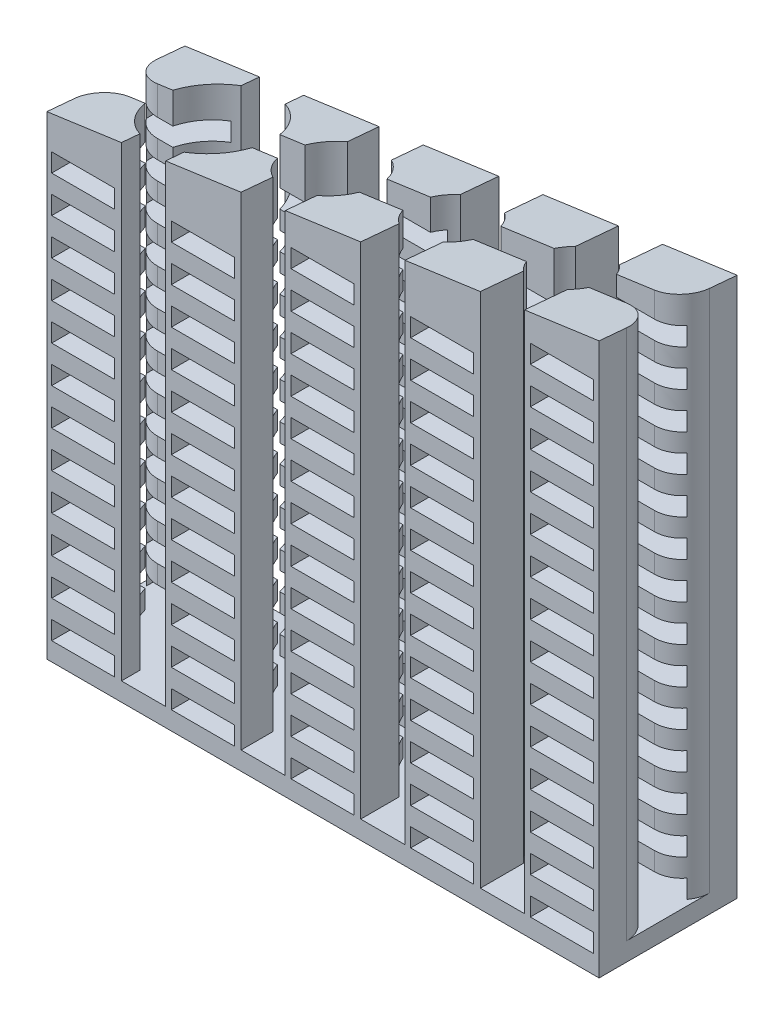
SolidWorks part; units mm, degrees
ref_plane "Front Plane" through (0, 0, 0) normal (0, 0, 1) x (1, 0, 0)
ref_plane "Top Plane" through (0, 0, 0) normal (0, 1, 0) x (1, 0, 0)
ref_plane "Right Plane" through (0, 0, 0) normal (1, 0, 0) x (0, 0, -1)
sketch "Sketch2" plane through (0, 0, 0) normal (0, 1, 0) x (1, 0, 0)
  line L1 (-9.8739, 6.0125) -> (-162.2739, 6.0125)
  line L2 (-9.8739, 6.0125) -> (-9.8739, 44.1125)
  line L3 (-9.8739, 44.1125) -> (-162.2739, 44.1125)
  line L4 (-162.2739, 6.0125) -> (-162.2739, 44.1125)
  dimension "D1" = 152.4
  dimension "D2" = 38.1
extrude "Boss-Extrude1" add sketch "Sketch2" along normal blind 152.4
sketch "Sketch3" plane through (0, 152.4, 0) normal (0, 1, 0) x (1, 0, 0)
  line L0 (-162.2739, 25.0625) -> (-9.8739, 25.0625) construction
  line L1 (-162.2739, 44.1125) -> (-162.2739, 6.0125) construction
  line L2 (-9.8739, 6.0125) -> (-9.8739, 44.1125) construction
  circle A0 centre (-36.5439, 25.0625) radius 9.398
  circle A1 centre (-69.5639, 25.0625) radius 10.414
  circle A2 centre (-102.5839, 25.0625) radius 11.938
  circle A3 centre (-135.6039, 25.0625) radius 15.24
  dimension "D1" = 18.796
  dimension "D2" = 20.828
  dimension "D3" = 23.876
  dimension "D4" = 30.48
  dimension "D5" = 26.67
  dimension "D6" = 33.02
  dimension "D7" = 33.02
  dimension "D8" = 33.02
  dimension "D9" = 26.67
extrude "Cut-Extrude1" cut sketch "Sketch3" against normal offset from surface (147.32 mm away) 5.08 up to face at (-86.0739, 0, -25.0625)
ref_plane "Plane1" through (-24.1467, 171.8125, 0) normal (-0.1392, 0.9903, 0) x (0.9903, 0.1392, 0)
sketch "Sketch6" plane through (-24.1467, 171.8125, 0) normal (-0.1392, 0.9903, 0) x (0.9903, 0.1392, 0)
  line L1 (-170.4577, 63.4342) -> (31.4648, 63.4342)
  line L2 (-170.4577, 63.4342) -> (-170.4577, -17.9499)
  line L3 (-170.4577, -17.9499) -> (31.4648, -17.9499)
  line L4 (31.4648, 63.4342) -> (31.4648, -17.9499)
extrude "Cut-Extrude12" cut sketch "Sketch6" against normal blind 21.336
sketch "Sketch7" plane through (0, 0, -6.0125) normal (0, 0, 1) x (1, 0, 0)
  line L1 (-42.6399, 157.9878) -> (-30.4479, 157.9878)
  line L2 (-42.6399, 157.9878) -> (-42.6399, 5.08)
  line L3 (-42.6399, 5.08) -> (-30.4479, 5.08)
  line L4 (-30.4479, 157.9878) -> (-30.4479, 5.08)
  line L7 (-9.8739, 152.2727) -> (-9.8739, 0) construction
  line L9 (-162.2739, 0) -> (-9.8739, 0) construction
  dimension "D1" = 20.574
  dimension "D2" = 12.192
  dimension "D3" = 5.08
extrude "Cut-Extrude13" cut sketch "Sketch7" against normal blind 59.69 contours L2 L3 L4 L1
pattern_linear "LPattern1" count 4 spacing 33.02 along (-1, 0, 0) of "Cut-Extrude13"
sketch "Sketch8" plane through (-9.8739, 0, 0) normal (1, 0, 0) x (0, 0, -1)
  line L0 (6.0125, 0) -> (44.1125, 0) construction
  line L1 (21.2525, 5.08) -> (28.8725, 5.08)
  line L2 (21.2525, 5.08) -> (21.2525, 164.0227)
  line L3 (21.2525, 164.0227) -> (28.8725, 164.0227)
  line L4 (28.8725, 5.08) -> (28.8725, 164.0227)
  line L5 (44.1125, 152.2727) -> (44.1125, 0) construction
  line L6 (6.0125, 152.2727) -> (6.0125, 0) construction
  dimension "D1" = 5.08
  dimension "D2" = 7.62
  dimension "D3" = 15.24
  dimension "D4" = 15.24
extrude "Cut-Extrude14" cut sketch "Sketch8" against normal blind 199.136 contours L3 L4 L1 L2
sketch "Sketch9" plane through (0, 0, -6.0125) normal (0, 0, 1) x (1, 0, 0)
  line L1 (-28.8604, 10.16) -> (-11.4614, 10.16)
  line L2 (-28.8604, 10.16) -> (-28.8604, 5.08)
  line L3 (-28.8604, 5.08) -> (-11.4614, 5.08)
  line L4 (-11.4614, 10.16) -> (-11.4614, 5.08)
  line L6 (-30.4479, 149.3813) -> (-30.4479, 5.08) construction
  line L7 (-9.8739, 152.2727) -> (-9.8739, 0) construction
  line L8 (-162.2739, 0) -> (-9.8739, 0) construction
  dimension "D1" = 1.5875
  dimension "D2" = 1.5875
  dimension "D3" = 5.08
  dimension "D4" = 5.08
extrude "Cut-Extrude15" cut sketch "Sketch9" against normal blind 199.136
pattern_linear "LPattern2" count 5 spacing 33.02 along (-1, 0, 0) count 14 spacing 10.16 along (0, 1, 0) skipping (1, 13), (2, 13), (3, 12), (3, 13), (4, 12), (4, 13) of "Cut-Extrude15"
fillet "Fillet2" radius 7.62 4 edges at (-162.2739, 67.9672, -21.2525) (-162.2739, 67.9672, -28.8725) (-9.8739, 78.6764, -21.2525) (-9.8739, 78.6764, -28.8725)
ref_plane "Plane2" through (-21.0891, 150.0565, -13.2573) normal (-0.1386, 0.9865, -0.0872) x (0.9903, 0.1392, 0)
sketch "Sketch10" plane through (-21.0891, 150.0565, -13.2573) normal (-0.1386, 0.9865, -0.0872) x (0.9903, 0.1392, 0)
  line L1 (-199.7047, -26.8172) -> (43.2114, -26.8172)
  line L2 (-199.7047, -26.8172) -> (-199.7047, 85.1814)
  line L3 (-199.7047, 85.1814) -> (43.2114, 85.1814)
  line L4 (43.2114, -26.8172) -> (43.2114, 85.1814)
extrude "Cut-Extrude16" cut sketch "Sketch10" along normal blind 16.256 contours L1 L4 L3 L2
